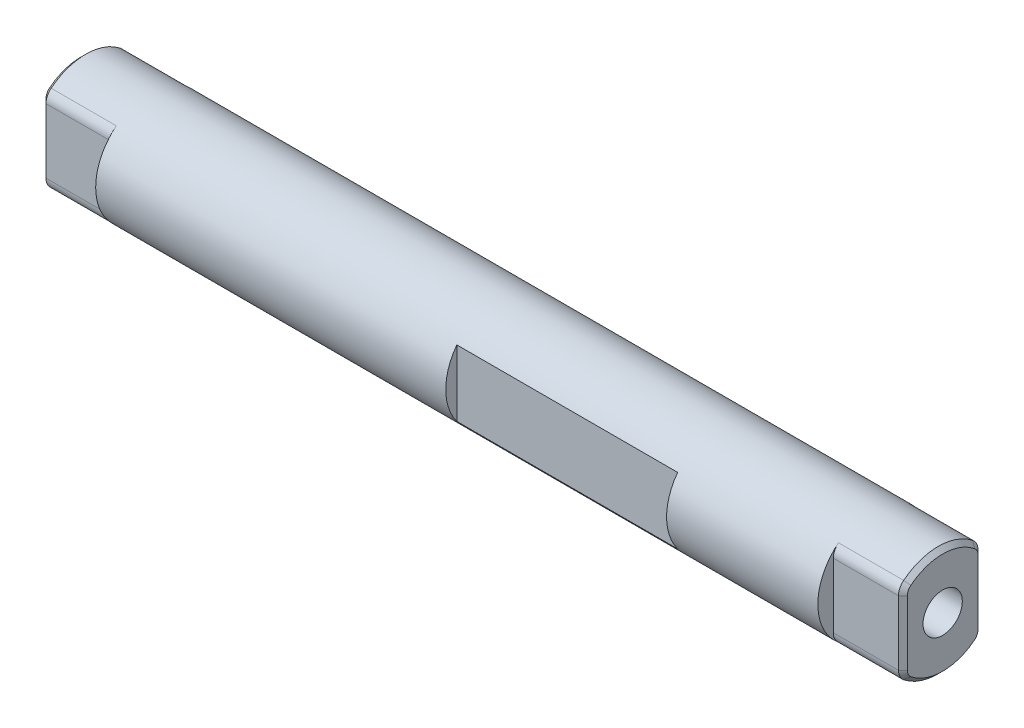
SolidWorks part; units mm, degrees
material "Plain Carbon Steel"
ref_plane "Front Plane" through (0, 0, 0) normal (0, 0, 1) x (1, 0, 0)
ref_plane "Top Plane" through (0, 0, 0) normal (0, 1, 0) x (1, 0, 0)
ref_plane "Right Plane" through (0, 0, 0) normal (1, 0, 0) x (0, 0, -1)
sketch "Sketch1" plane through (0, 0, 0) normal (1, 0, 0) x (0, 0, -1)
  circle A0 centre (0, 0) radius 3.175
  dimension "D1" = 6.35
extrude "Boss-Extrude1" add sketch "Sketch1" along normal mid plane 41.529
sketch "Sketch2" plane through (20.7645, 0, 0) normal (1, 0, 0) x (0, 0, -1)
  line L0 (-2.286, 2.2034) -> (-2.286, -2.2034)
  line L1 (2.286, 2.2034) -> (2.286, -2.2034)
  circle A0 centre (0, 0) radius 3.175 construction
  circle A1 centre (0, 0) radius 3.175
  arc A2 (-2.286, -2.2034) -> (2.286, -2.2034) centre (0, 0) ccw
  arc A3 (2.286, 2.2034) -> (-2.286, 2.2034) centre (0, 0) ccw
  dimension "D2" = 2.286
  dimension "D3" = 2.286
  dimension "D1" = 0
extrude "Boss-Extrude2" add sketch "Sketch2" along normal blind 4.0005
fillet "Fillet1" radius 0.7937 4 edges
hole_wizard "#4-40 Tapped Hole1" positions "Sketch4" profile "Sketch3" tap size "#4-40" standard "Ansi Inch"
sketch "Sketch4" plane through (24.765, 0, 0) normal (1, 0, 0) x (0, 0, -1)
  point P0 (0, 0)
sketch "Sketch3" plane through (24.765, 0, 0) normal (0, 1, 0) x (0, 0, -1)
  line L0 (0, 0) -> (0, 8.2992)
  line L1 (0, 8.2992) -> (1.1303, 7.62)
  line L2 (1.1303, 7.62) -> (1.1303, 0)
  line L5 (1.1303, 0) -> (0, 0)
  line L10 (0, 8.2992) -> (-1.1303, 7.62) construction
  line L11 (0, -6.35) -> (0, 107.95) construction
  dimension "Tap Drill Dia." = 2.2606
  dimension "Tap Drill Depth" = 7.62
  dimension "Drill Angle" = 118
cosmetic thread "Hole Thread1" parameters "D1"=5.588, "D2"=2.8448
chamfer "Chamfer1" distance 0.254 angle 45 8 edges at (24.765, 0, 2.286) (24.765, -2.1986, 2.2081) (24.765, 2.1986, 2.2081) (24.765, -3.175, 0) (24.765, 3.175, 0) (24.765, -2.1986, -2.2081) (24.765, 2.1986, -2.2081) (24.765, 0, -2.286)
mirror "Mirror2" about plane through (0, 0, 0) normal (1, 0, 0) of "Boss-Extrude2", "Fillet1", "#4-40 Tapped Hole1", "Chamfer1"
ref_plane "Plane1" through (0, 0, 3.175) normal (0, 0, 1) x (1, 0, 0)
sketch "Sketch5" plane through (0, 0, 3.175) normal (0, 0, 1) x (1, 0, 0)
  line L0 (-0.635, 0) -> (12.065, 0) construction
  line L1 (-0.635, -3.175) -> (12.065, -3.175)
  line L2 (-0.635, -3.175) -> (-0.635, 3.175)
  line L3 (-0.635, 3.175) -> (12.065, 3.175)
  line L4 (12.065, -3.175) -> (12.065, 3.175)
  line L5 (24.765, 1.8557) -> (24.765, -1.8557) construction
  point P0 (0, 0)
  dimension "D1" = 12.7
  dimension "D2" = 6.35
  dimension "D3" = 12.7
extrude "Cut-Extrude1" cut sketch "Sketch5" against normal blind 0.635
